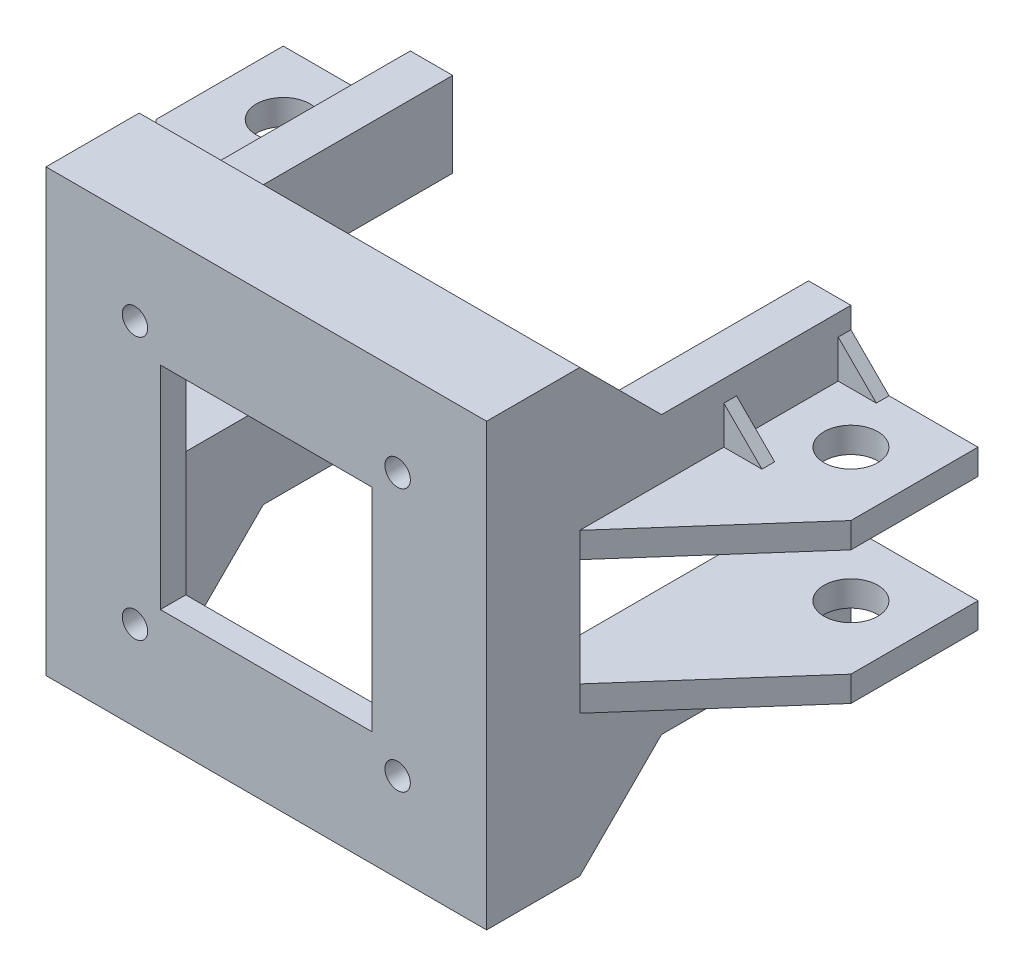
SolidWorks part; units mm, degrees
material "ABS"
ref_plane "Front Plane" through (0, 0, 0) normal (0, 0, 1) x (1, 0, 0)
ref_plane "Top Plane" through (0, 0, 0) normal (0, 1, 0) x (1, 0, 0)
ref_plane "Right Plane" through (0, 0, 0) normal (1, 0, 0) x (0, 0, -1)
sketch "Sketch1" plane through (0, 0, 0) normal (0, 0, 1) x (1, 0, 0)
  line L0 (-21, 16.5699) -> (-21, -16.5699) construction
  line L1 (-21, 21) -> (21, 21)
  line L2 (-21, 21) -> (-21, -21)
  line L3 (-21, -21) -> (21, -21)
  line L4 (21, 21) -> (21, -21)
  line L5 (-21, 21) -> (21, -21) construction
  line L6 (-21, -21) -> (21, 21) construction
  line L7 (-26, 26) -> (26, 26)
  line L8 (-26, 26) -> (-26, -26)
  line L9 (-26, -26) -> (26, -26)
  line L10 (26, 26) -> (26, -26)
  line L11 (-26, 26) -> (26, -26) construction
  line L12 (-26, -26) -> (26, 26) construction
  line L13 (16.5699, 21) -> (-16.5699, 21) construction
  point P0 (0, 0)
  point P6 (0, 0)
  dimension "D1" = 5
  dimension "D2" = 5
extrude "Boss-Extrude1" add sketch "Sketch1" against normal blind 8
sketch "Sketch3" plane through (0, 0, -8) normal (0, 0, -1) x (-1, 0, 0)
  line L0 (-26, -26) -> (-26, 26) construction
  line L1 (-26, 6.35) -> (-21, 6.35)
  line L2 (-26, 6.35) -> (-26, 16.35)
  line L3 (-26, 16.35) -> (-21, 16.35)
  line L4 (-21, 6.35) -> (-21, 16.35)
  line L5 (-21, -21) -> (-21, 21) construction
  line L6 (0, 0) -> (-30.2429, 0) construction
  line L7 (-26, -16.35) -> (-21, -16.35)
  line L8 (-21, -6.35) -> (-21, -16.35)
  line L9 (-26, -6.35) -> (-26, -16.35)
  line L10 (-26, -6.35) -> (-21, -6.35)
  dimension "D1" = 10
  dimension "D2" = 6.35
extrude "Boss-Extrude3" add sketch "Sketch3" along normal blind 32
sketch "Sketch4" plane through (26, 0, 0) normal (1, 0, 0) x (0, 0, -1)
  line L0 (40, -6.35) -> (8, -6.35) construction
  line L1 (25, -6.35) -> (40, -6.35)
  line L2 (25, -6.35) -> (25, -9.35)
  line L3 (25, -9.35) -> (40, -9.35)
  line L4 (40, -6.35) -> (40, -9.35)
  line L5 (40, -6.35) -> (40, -16.35) construction
  dimension "D1" = 3
  dimension "D2" = 15
extrude "Boss-Extrude4" add sketch "Sketch4" along normal blind 15
mirror "Mirror1" about plane through (0, 0, 0) normal (0, 1, 0) of "Boss-Extrude4"
mirror "Mirror2" about plane through (0, 0, 0) normal (1, 0, 0) of "Boss-Extrude3", "Boss-Extrude4", "Mirror1"
sketch "Sketch2" plane through (0, 0, 0) normal (0, 0, 1) x (1, 0, 0)
  line L0 (-26, -26) -> (26, -26) construction
  line L1 (-12.5, 12.5) -> (12.5, 12.5)
  line L2 (-12.5, 12.5) -> (-12.5, -12.5)
  line L3 (-12.5, -12.5) -> (12.5, -12.5)
  line L4 (12.5, 12.5) -> (12.5, -12.5)
  line L5 (-12.5, 12.5) -> (12.5, -12.5) construction
  line L6 (-12.5, -12.5) -> (12.5, 12.5) construction
  line L7 (-26, 26) -> (26, 26)
  line L8 (-26, 26) -> (-26, -26)
  line L9 (-26, -26) -> (26, -26)
  line L10 (26, 26) -> (26, -26)
  line L11 (-26, 26) -> (26, -26) construction
  line L12 (-26, -26) -> (26, 26) construction
  line L13 (26, -26) -> (26, 26) construction
  point P0 (0, 0)
  point P6 (0, 0)
  dimension "D1" = 25
  dimension "D2" = 25
extrude "Boss-Extrude2" add sketch "Sketch2" along normal blind 3
hole_wizard "1/4 (0.25) Diameter Hole1" positions "Sketch6" profile "Sketch7" hole size "1/4" standard "ANSI Inch" end condition through all
sketch "Sketch6" plane through (0, -9.35, 0) normal (0, -1, 0) x (-1, 0, 0)
  line L0 (41, 25) -> (41, 40) construction
  line L1 (41, 25) -> (26, 25) construction
  point P0 (33.5, 32.5)
  dimension "D1" = 7.5
  dimension "D2" = 7.5
sketch "Sketch7" plane through (-33.5, -9.35, -32.5) normal (1, 0, 0) x (0, 0, -1)
  line L0 (0, 0) -> (0, 35.35)
  line L1 (0, 35.35) -> (3.175, 35.35)
  line L2 (3.175, 35.35) -> (3.175, 0)
  line L5 (3.175, 0) -> (0, 0)
  line L11 (0, -6.35) -> (0, 107.95) construction
  dimension "Thru Hole Dia." = 6.35
  dimension "Thru Hole Depth" = 35.35
mirror "Mirror3" about plane through (0, 0, 0) normal (1, 0, 0) of "1/4 (0.25) Diameter Hole1"
sketch "Sketch9" plane through (-26, 0, 0) normal (-1, 0, 0) x (0, 0, 1)
  line L0 (-8, -26) -> (-17.65, -16.35)
  line L1 (-40, -16.35) -> (-8, -16.35) construction
  line L2 (-8, -16.35) -> (-8, -26) construction
  dimension "D1" = 45
rib "Rib1" sketch "Sketch9" sketch "Sketch9" thickness 5 extrusion direction parallel to sketch draft on no parameters "D1"=5
mirror "Mirror4" about plane through (0, 0, 0) normal (0, 1, 0) of "Rib1"
mirror "Mirror5" about plane through (0, 0, 0) normal (1, 0, 0) of "Rib1", "Mirror4"
hole_wizard "Ø3.0mm Dowel Hole1" positions "Sketch10" profile "Sketch11" hole size "Ø3.0" standard "ANSI Metric" end condition through all
sketch "Sketch10" plane through (0, 0, 0) normal (0, 0, -1) x (-1, 0, 0)
  point P0 (15.5, -15.5)
  point P3 (-15.5, -15.5)
  point P6 (-15.5, 15.5)
  point P9 (15.5, 15.5)
sketch "Sketch11" plane through (-15.5, -15.5, 0) normal (1, 0, 0) x (0, 1, 0)
  line L0 (0, 0) -> (0, 3)
  line L1 (0, 3) -> (1.5, 3)
  line L2 (1.5, 3) -> (1.5, 0)
  line L5 (1.5, 0) -> (0, 0)
  line L11 (0, -6.35) -> (0, 107.95) construction
  dimension "Thru Hole Dia." = 3
  dimension "Thru Hole Depth" = 3
sketch "Sketch12" plane through (0, 0, -25) normal (0, 0, 1) x (1, 0, 0)
  line L0 (-30.5, -9.35) -> (-26, -13.85)
  line L1 (-41, -9.35) -> (-26, -9.35) construction
  line L3 (-26, 6.35) -> (-26, 9.35) construction
  line L4 (-26, -13.85) -> (-26, -9.35)
  line L5 (-26, -9.35) -> (-30.5, -9.35)
  dimension "D1" = 4.5
  dimension "D2" = 4.5
extrude "Boss-Extrude5" add sketch "Sketch12" against normal blind 1.5 contours L0 L4 L5
extrude "Boss-Extrude6" add sketch "Sketch12<3>" along normal blind 1.5 from surface starting at face at (-29.3333, -10.6833, -40)
sketch "Sketch12<3>" plane through (0, 0, -25) normal (0, 0, 1) x (1, 0, 0) same geometry as "Sketch12"
mirror "Mirror6" about plane through (0, 0, 0) normal (1, 0, 0) of "Boss-Extrude5", "Boss-Extrude6"
mirror "Mirror7" about plane through (0, 0, 0) normal (0, 1, 0) of "Mirror6"
sketch "Sketch13" plane through (0, -6.35, 0) normal (0, 1, 0) x (1, 0, 0)
  line L0 (-26, 8) -> (-41, 25)
rib "Rib12" sketch "Sketch13" sketch "Sketch13" thickness 3 extrusion direction parallel to sketch draft on no parameters "D1"=3
mirror "Mirror8" about plane through (0, 0, 0) normal (0, 1, 0) of "Rib12"
mirror "Mirror9" about plane through (0, 0, 0) normal (1, 0, 0) of "Mirror8"
